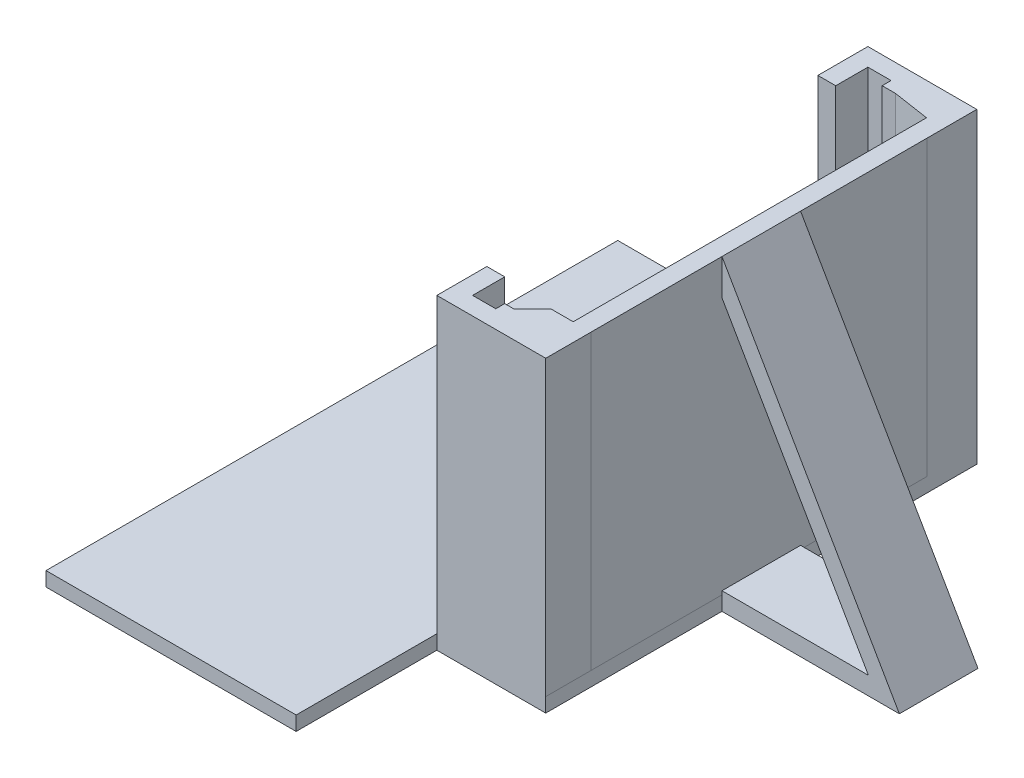
SolidWorks part; units mm, degrees
ref_plane "Front Plane" through (0, 0, 0) normal (0, 0, 1) x (1, 0, 0)
ref_plane "Top Plane" through (0, 0, 0) normal (0, 1, 0) x (1, 0, 0)
ref_plane "Right Plane" through (0, 0, 0) normal (1, 0, 0) x (0, 0, -1)
sketch "Sketch1" plane through (0, 0, 0) normal (0, 1, 0) x (1, 0, 0)
  line L1 (0, 0) -> (38.6999, 0)
  line L2 (0, 0) -> (0, 153.1937)
  line L3 (0, 153.1937) -> (38.6999, 153.1937)
  line L4 (38.6999, 0) -> (38.6999, 153.1937)
  line L5 (0, 153.1937) -> (-88.9, 153.1937)
  line L6 (0, 153.1937) -> (0, -50.0063)
  line L7 (0, -50.0063) -> (-88.9, -50.0063)
  line L8 (-88.9, 153.1937) -> (-88.9, -50.0063)
  dimension "D1" = 38.6999
  dimension "D2" = 153.1937
  dimension "D3" = 88.9
  dimension "D4" = 203.2
extrude "Boss-Extrude1" add sketch "Sketch1" along normal blind 5.08 contours L1 L4 L3 L2 | L5 L8 L7 L6 L2 region at (19.35, 0, -76.5969) region at (-44.45, 0, -51.5937)
sketch "Sketch3" plane through (0, 5.08, 0) normal (0, 1, 0) x (1, 0, 0)
  line L0 (6.65, 146.8438) -> (6.35, 146.8438)
  line L1 (6.65, 146.8438) -> (14.5875, 146.8438)
  line L2 (14.5875, 146.8438) -> (14.5875, 143.6687)
  line L3 (14.5875, 143.6687) -> (32.05, 143.6687)
  line L4 (6.35, 146.8438) -> (6.35, 135.4137)
  line L7 (32.05, 143.6687) -> (32.35, 143.6687)
  line L8 (32.35, 143.6687) -> (32.35, 135.4137)
  line L9 (32.35, 135.4137) -> (38.7, 135.4137)
  line L10 (38.7, 135.4137) -> (38.7, 153.1937)
  line L11 (38.7, 153.1937) -> (0, 153.1937)
  line L12 (6.35, 135.4137) -> (0, 135.4137)
  line L13 (0, 153.1937) -> (0, 135.4137)
  line L14 (-88.9, 153.1937) -> (38.6999, 153.1937) construction
  line L16 (14.5875, 9.525) -> (17.7625, 9.525)
  line L17 (10.6187, 146.8438) -> (10.6187, 76.5969) construction
  line L18 (10.6187, 76.5969) -> (61.4187, 76.5969) construction
  line L19 (38.6999, 0) -> (0, 0)
  line L20 (38.6999, 16.1157) -> (38.6999, 0)
  line L25 (14.5875, 6.35) -> (14.5875, 9.525)
  line L26 (6.65, 6.35) -> (14.5875, 6.35)
  line L27 (6.65, 6.35) -> (6.35, 6.35)
  line L28 (6.35, 6.35) -> (6.35, 17.78)
  line L29 (6.35, 17.78) -> (0, 17.78)
  line L30 (0, 0) -> (0, 17.78)
  line L31 (17.7625, 9.525) -> (24.3532, 16.1157)
  line L32 (24.3532, 16.1157) -> (38.6999, 16.1157)
  line L33 (19.35, 143.6687) -> (32.35, 141.6844)
  line L34 (38.6999, 0) -> (38.6999, 153.1937) construction
  point P14 (0, 0)
  point P19 (10.6187, 146.8438)
  dimension "D1" = 17.4625
  dimension "D2" = 7.9375
  dimension "D3" = 3.175
  dimension "D4" = 11.43
  dimension "D5" = 0.3
  dimension "D6" = 0.3
  dimension "D7" = 0
  dimension "D8" = 38.6999
  dimension "D9" = 6.35
  dimension "D10" = 6.35
  dimension "D11" = 6.35
  dimension "D12" = 6.35
  dimension "D13" = 70.2469
  dimension "D14" = 50.8
  dimension "D15" = 3.175
  dimension "D16" = 135
  dimension "D17" = 14.3467
  dimension "D18" = 90
  dimension "D19" = 18.08
  dimension "D20" = 90
  dimension "D21" = 4.7625
  dimension "D22" = 1.9844
extrude "Boss-Extrude2" add sketch "Sketch3" along normal blind 104.14 contours L13 L12 L4 L0 L1 L2 L3 L7 L8 L9 L10 | L30 L19 L20 L25 L26 L27 L28 L29 | L3 L33 L8 L7 region at (19.8693, 5.08, -146.5333) region at (28.0167, 5.08, -143.0073) region at (20.5173, 5.08, -7.298)
sketch "Sketch6" plane through (0, 0, -135.4137) normal (0, 0, 1) x (1, 0, 0)
  line L1 (32.35, 109.22) -> (38.7, 109.22)
  line L2 (32.35, 109.22) -> (32.35, 5.08)
  line L3 (32.35, 5.08) -> (38.7, 5.08)
  line L4 (38.7, 109.22) -> (38.7, 5.08)
  dimension "D1" = 104.14
  dimension "D2" = 6.35
extrude "Boss-Extrude3" add sketch "Sketch6" along normal up to surface (119.298 mm away) up to face at (31.5266, 57.15, -16.1157)
sketch "Sketch11" plane through (0, 0, -153.1937) normal (0, 0, -1) x (-1, 0, 0)
  line L0 (-38.6999, 109.22) -> (-101.7581, 0)
  line L1 (-38.6999, 109.22) -> (-38.6999, 0) construction
  line L4 (-38.6999, 96.52) -> (-94.4258, 0)
  line L5 (-94.4258, 0) -> (-101.7581, 0)
  line L6 (-38.6999, 96.52) -> (-38.6999, 109.22)
  line L8 (-38.6999, 109.22) -> (0, 109.22) construction
  line L9 (88.9, 0) -> (-38.6999, 0) construction
  dimension "D1" = 0
  dimension "D2" = 30
  dimension "D3" = 0
  dimension "D4" = 30
  dimension "D6" = 12.7
extrude "Boss-Extrude5" add sketch "Sketch11" along direction (0, 0, -1) on the side against the normal blind 27.94 from offset 62.6269 contours L6 L0 L5 L4 offset against normal yes
sketch "Sketch13" plane through (38.6999, 0, 0) normal (1, 0, 0) x (0, 0, -1)
  line L0 (0, 0) -> (153.1937, 0) construction
  line L1 (90.5669, 0) -> (62.6269, 0)
  line L2 (90.5669, 0) -> (90.5669, 6.35)
  line L3 (90.5669, 6.35) -> (62.6269, 6.35)
  line L4 (62.6269, 0) -> (62.6269, 6.35)
  line L5 (90.5669, 96.5199) -> (90.5669, 0) construction
  line L6 (62.6269, 109.2199) -> (62.6269, 0) construction
  dimension "D1" = 0
  dimension "D2" = 0
  dimension "D3" = 6.35
  dimension "D4" = 6.35
extrude "Boss-Extrude6" add sketch "Sketch13" along normal up to surface (63.0582 mm away) up to face at (70.2291, 54.61, -76.5969)
sketch "Sketch14" plane through (0, 0, -153.1937) normal (0, 0, -1) x (-1, 0, 0)
  line L0 (-14.5875, 5.08) -> (-6.35, 5.08) construction
  line L1 (-26, 36.83) -> (-14.5875, 36.83)
  line L2 (-26, 36.83) -> (-26, 55.88)
  line L3 (-26, 55.88) -> (-14.5875, 55.88)
  line L4 (-14.5875, 36.83) -> (-14.5875, 55.88)
  line L5 (88.9, 5.08) -> (0, 5.08) construction
  line L6 (-14.5875, 109.22) -> (-14.5875, 5.08) construction
  line L7 (-32.35, 109.22) -> (-32.35, 5.08) construction
  dimension "D1" = 31.75
  dimension "D2" = 50.8
  dimension "D3" = 0
  dimension "D4" = 6.35
extrude "Cut-Extrude1" cut sketch "Sketch14" against normal up to next
